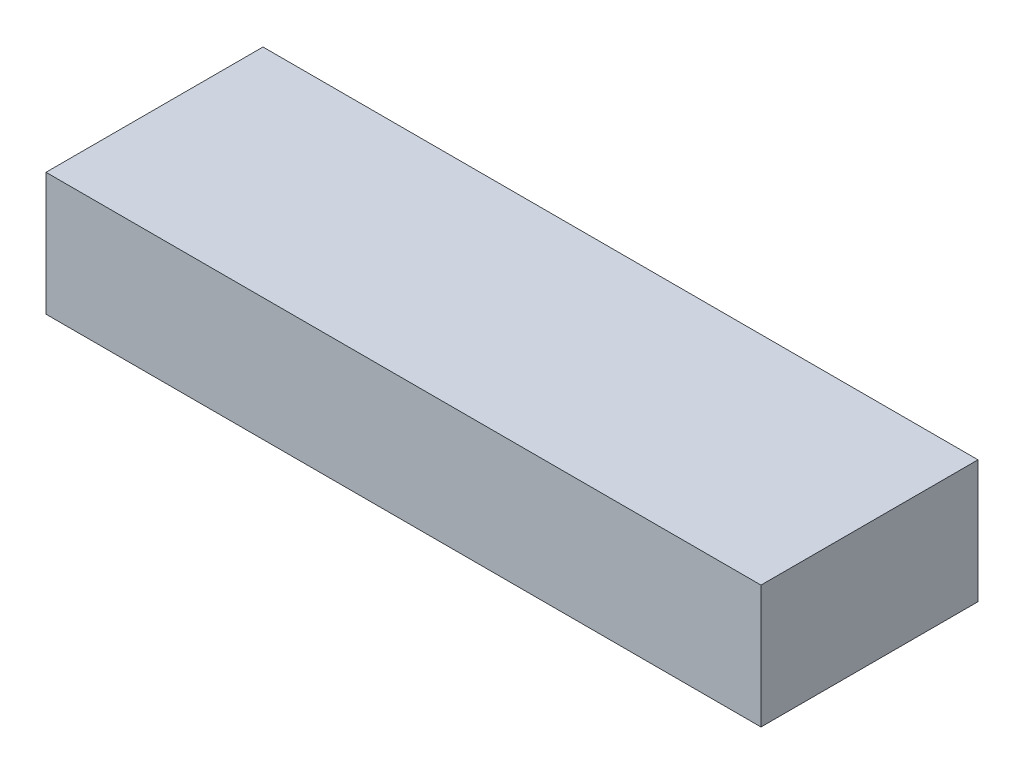
SolidWorks part; units mm, degrees
ref_plane "Front Plane" through (0, 0, 0) normal (0, 0, 1) x (1, 0, 0)
ref_plane "Top Plane" through (0, 0, 0) normal (0, 1, 0) x (1, 0, 0)
ref_plane "Right Plane" through (0, 0, 0) normal (1, 0, 0) x (0, 0, -1)
sketch "Sketch1" plane through (0, 0, 0) normal (0, 1, 0) x (1, 0, 0)
  line L1 (570, -173) -> (-570, -173)
  line L2 (570, -173) -> (570, 173)
  line L3 (570, 173) -> (-570, 173)
  line L4 (-570, -173) -> (-570, 173)
  line L5 (570, -173) -> (-570, 173) construction
  line L6 (570, 173) -> (-570, -173) construction
  point P0 (0, 0)
  dimension "D1" = 1140
  dimension "D2" = 346
extrude "Boss-Extrude1" add sketch "Sketch1" along normal blind 196
equation "\"assembly\"= 0"
equation "\"thickness 1\" = 2"
equation "\"thickness 2\" = 8"
equation "\"connecting flange\" = 35"
equation "\"main\"= 0"
equation "\"main length\" = 1200"
equation "\"main width\" = 1200"
equation "\"divider panel distance offset\" = 346"
equation "\"side panel\"= 0"
equation "\"access hatch length\" = 600"
equation "\"access hatch width\" = 450"
equation "\"access hatch offset X\" = 100"
equation "\"access hatch offset Y\" = 100"
equation "\"side panel length\" = 1200"
equation "\"side panel width\" = 1000"
equation "\"back panel\"= 0"
equation "\"back panel access hatch length\" = 1150"
equation "\"back panel access hatch width\" = 206"
equation "\"back panel access hatch flange\" = 40"
equation "\"drift eliminator\"= 0"
equation "\"drift eliminator size offset\" = 10"
equation "\"drift eliminator length\" = \"back panel access hatch length\" - \"drift eliminator size offset\""
equation "\"drift eliminator width\" = \"back panel access hatch width\" - \"drift eliminator size offset\""
equation "\"drift eliminator depth\" = \"divider panel distance offset\""
equation "\"sump\" = 0"
equation "\"D1@Boss-Extrude1\"=\"drift eliminator width\""
equation "\"D1@Sketch1\"=\"drift eliminator length\""
equation "\"D2@Sketch1\"=\"drift eliminator depth\""
